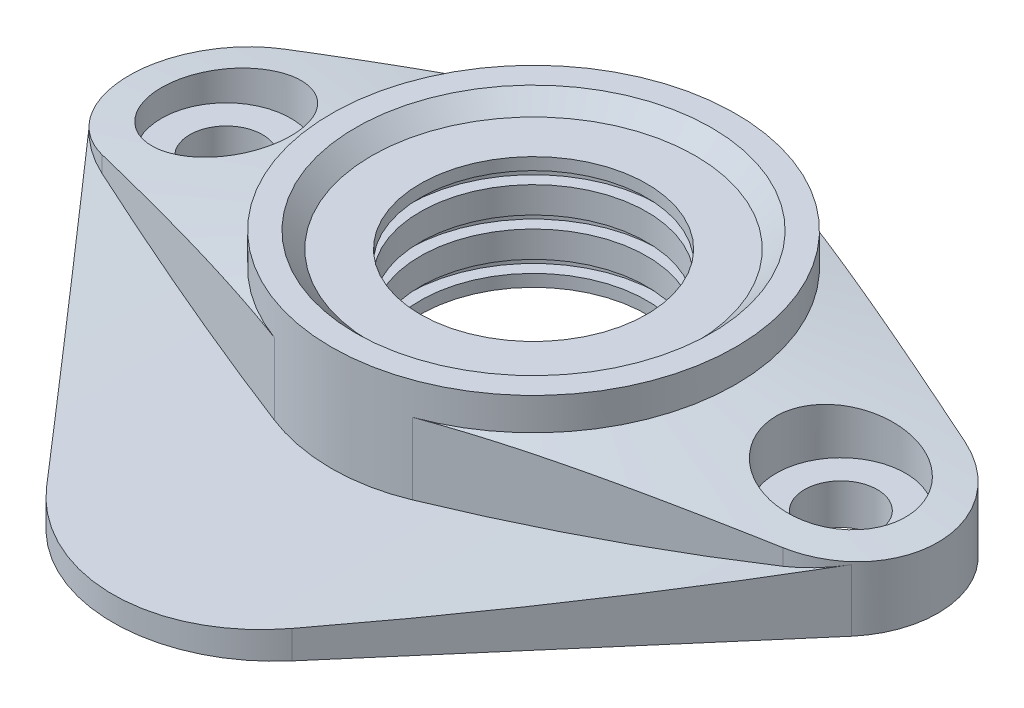
SolidWorks part; units mm, degrees
note: The reader was unsure of these and kept them because the rebuilt part matched: shared geometry of "草图1<4>", "草图1<7>".
ref_plane "前视基准面" through (0, 0, 0) normal (0, 0, 1) x (1, 0, 0)
ref_plane "上视基准面" through (0, 0, 0) normal (0, 1, 0) x (1, 0, 0)
ref_plane "右视基准面" through (0, 0, 0) normal (1, 0, 0) x (0, 0, -1)
other "Configuration Table"
sketch "草图1" plane through (0, 0, 0) normal (0, 1, 0) x (1, 0, 0)
  line L0 (-38, 0) -> (40.0781, 0) construction
  line L1 (0, 25) -> (0, -52) construction
  line L2 (-42.1053, 11.2759) -> (-8.5526, 23.4915)
  line L3 (-42.1053, -11.2759) -> (-8.5526, -23.4915)
  line L4 (42.1053, -11.2759) -> (8.5526, -23.4915)
  line L5 (42.1053, 11.2759) -> (8.5526, 23.4915)
  line L6 (-47.1069, -7.8144) -> (-15.1781, -45.024)
  line L7 (47.1069, -7.8144) -> (15.1781, -45.024)
  circle A0 centre (0, 0) radius 25
  circle A1 centre (0, 0) radius 14
  arc A2 (-42.1053, 11.2759) -> (-42.1053, -11.2759) centre (-38, 0) ccw
  arc A3 (42.1053, 11.2759) -> (42.1053, -11.2759) centre (38, 0) cw
  arc A4 (-15.1781, -45.024) -> (15.1781, -45.024) centre (0, -32) ccw
  dimension "D1" = 12
  dimension "D2" = 50
  dimension "D3" = 76
  dimension "D4" = 28
  dimension "D5" = 20
  dimension "D6" = 77
extrude "凸台-拉伸1" add sketch "草图1" along normal blind 16 contours A0 A1
sketch "草图2" plane through (0, 0, 0) normal (0, 0, 1) x (1, 0, 0)
  line L0 (25, 12) -> (62.2105, 5.4388)
  line L1 (25, 0) -> (25, 16) construction
  line L2 (25, 16) -> (-25, 16) construction
  line L3 (0, 0) -> (0, 32.423) construction
  dimension "D1" = 4
  dimension "D2" = 100
ref_plane "基准面1" through (2.806, 15.9134, 0) normal (-0.1736, -0.9848, 0) x (0.9848, -0.1736, 0)
surface "曲面-旋转1" sketch "草图2" parameters "D1"=360
extrude "凸台-拉伸3" add sketch "草图1<4>" along normal up to surface (8.7223 mm away) contours A3 L5 A0 L4 | L2 A2 L3 A0
sketch "草图1<4>" plane through (0, 0, 0) normal (0, 1, 0) x (1, 0, 0) same geometry as "草图1"
delete or keep bodies "实体-删除/保留 1" type delete bodies bodies 116
sketch "草图7" plane through (0, 0, 0) normal (0, 0, 1) x (1, 0, 0)
  line L0 (0, 0) -> (0, 243) construction
  line L1 (15.1781, 0) -> (-15.1781, 0) construction
  arc A1 (-102.4537, 25.9672) -> (146.795, 53.1284) centre (0, 243) ccw
  dimension "D1" = 240
  dimension "D2" = 243
surface "曲面-拉伸1" sketch "草图7" parameters "D1"=100
extrude "凸台-拉伸4" add sketch "草图1<7>" along normal up to surface (7.6684 mm away) contours L6 A4 L7 A3 L4 A0 L3 A2
sketch "草图1<7>" plane through (0, 0, 0) normal (0, 1, 0) x (1, 0, 0) same geometry as "草图1"
delete or keep bodies "实体-删除/保留 2" type delete bodies bodies 118
hole_wizard "M8 六角头螺栓的柱形沉头孔1" positions "草图13" profile "草图14" counterbore size "M8" standard "GB" end condition through all
sketch "草图13" plane through (0, 16, 0) normal (0, 1, 0) x (1, 0, 0)
  point P0 (-38, 0)
sketch "草图14" plane through (-38, 16, 0) normal (1, 0, 0) x (0, 0, 1)
  line L0 (0, 0) -> (0, 16)
  line L1 (0, 16) -> (4.5, 16)
  line L3 (4.5, 16) -> (4.5, 11)
  line L4 (4.5, 11) -> (8, 11)
  line L5 (8, 11) -> (8, 0)
  line L7 (8, 0) -> (0, 0)
  line L11 (0, -6.35) -> (0, 107.95) construction
  dimension "通孔孔直径" = 9
  dimension "通孔孔深度" = 16
  dimension "柱形沉头孔直径" = 16
  dimension "柱形沉头孔深度" = 11
mirror "镜向1" about plane through (0, 0, 0) normal (1, 0, 0) of "M8 六角头螺栓的柱形沉头孔1"
sketch "草图15" plane through (0, 0, 0) normal (0, 1, 0) x (1, 0, 0)
  circle A2 centre (0, 0) radius 22
  circle A3 centre (0, 0) radius 22
  dimension "D1" = 3
extrude "切除-拉伸1" cut sketch "草图15" against normal blind 2 draft 45 from offset 16
sketch "草图16" plane through (0, 0, 0) normal (0, 0, 1) x (1, 0, 0)
  line L0 (0, 21.8065) -> (0, -5.34) construction
  line L1 (14, 0) -> (14, 14) construction
  line L10 (14, 12.5) -> (15.5, 12.5)
  line L11 (14, 12.5) -> (14, 11)
  line L12 (14, 11) -> (15.5, 11)
  line L13 (15.5, 12.5) -> (15.5, 11)
  line L14 (20, 14) -> (-20, 14) construction
  dimension "D1" = 1.5
  dimension "D2" = 1.5
  dimension "D3" = 1.5
revolve "切除-旋转5" cut sketch "草图16" angle 360 about L0
pattern_linear "阵列(线性)1" count 3 spacing 4.75 along (0, -1, 0) of "切除-旋转5"
